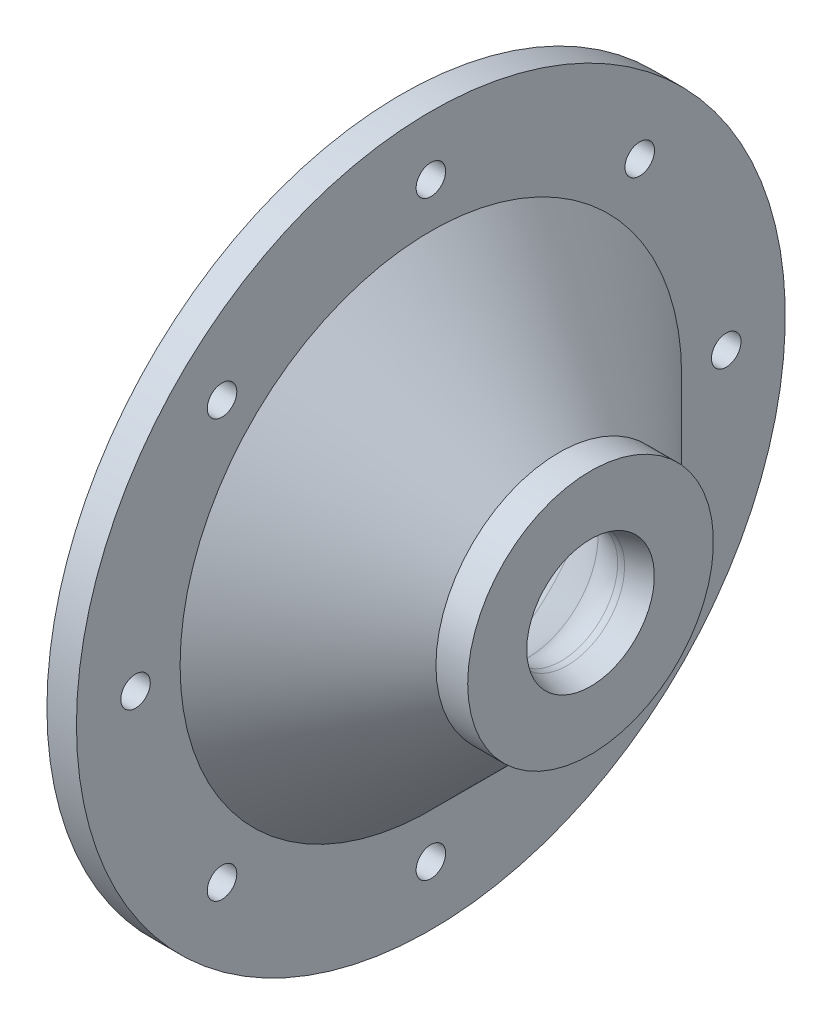
SolidWorks part; units mm, degrees
ref_plane "Front Plane" through (0, 0, 0) normal (0, 0, 1) x (1, 0, 0)
ref_plane "Top Plane" through (0, 0, 0) normal (0, 1, 0) x (1, 0, 0)
ref_plane "Right Plane" through (0, 0, 0) normal (1, 0, 0) x (0, 0, -1)
ref_axis "Axis1" through (-78.8197, 0, 0) along (1, 0, 0)
sketch "Sketch1" plane through (0, 0, 0) normal (0, 0, 1) x (1, 0, 0)
  line L1 (3.5921, 17.5621) -> (13.5703, 7.5839)
  line L2 (17.8198, 6.1825) -> (20.3406, 6.858)
  line L3 (0, 0) -> (4.5784, 0) construction
  line L4 (20.3406, 6.858) -> (20.3406, 13.208)
  line L5 (20.3406, 13.208) -> (16.9265, 13.208)
  line L6 (16.9265, 13.208) -> (3.175, 26.9595)
  line L10 (0, 19.05) -> (0, 38.1)
  line L11 (0, 38.1) -> (3.175, 38.1)
  line L12 (3.175, 38.1) -> (3.175, 26.9595)
  arc A0 (0, 19.05) -> (3.5921, 17.5621) centre (0, 13.97) cw
  arc A1 (13.5703, 7.5839) -> (17.1624, 6.096) centre (17.1624, 11.176) ccw
  arc A2 (17.1624, 6.096) -> (17.8198, 6.1825) centre (17.1624, 8.636) ccw
  point P13 (17.6181, 12.4785)
  point P16 (17.6248, 9.4173)
  point P18 (3.175, 22.4382)
  point P20 (5.8936, 19.8636)
  point P21 (7.1175, 21.0875)
  point P22 (5.6519, 19.6219)
  point P23 (3.175, 22.2985)
  point P24 (18.2958, 9.5971)
  point P25 (0, 0)
  point P26 (0, 0)
  point P27 (18.4132, 12.6915)
  point P28 (16.9593, 13.208)
  dimension "D1" = 5.08
  dimension "D6" = 2.54
  dimension "D7" = 5.08
  dimension "D4" = 6.096
  dimension "D5" = 6.858
  dimension "D9" = 19.05
  dimension "D11" = 38.1
  dimension "D12" = 3.175
  dimension "D8" = 6.35
  dimension "D10" = 6.35
  dimension "D2" = 45
  dimension "D3" = 15
revolve "Revolve1" add sketch "Sketch1" angle 360 about L3
hole_wizard "1/8 (0.125) Diameter Hole1" positions "Sketch2" profile "Sketch3" hole size "1/8" standard "ANSI Inch" end condition through all
sketch "Sketch2" plane through (3.175, 0, 0) normal (1, 0, 0) x (0, 0, -1)
  point P0 (0, 31.75)
  dimension "D1" = 31.75
sketch "Sketch3" plane through (3.175, 31.75, 0) normal (0, 1, 0) x (0, 0, -1)
  line L0 (0, 0) -> (0, 3.175)
  line L1 (0, 3.175) -> (1.5875, 3.175)
  line L2 (1.5875, 3.175) -> (1.5875, 0)
  line L5 (1.5875, 0) -> (0, 0)
  line L11 (0, -6.35) -> (0, 107.95) construction
  dimension "Thru Hole Dia." = 3.175
  dimension "Thru Hole Depth" = 3.175
pattern_circular "CirPattern1" count 8 over 360 about axis through (-78.8197, 0, 0) along (1, 0, 0) of "1/8 (0.125) Diameter Hole1"
equation "\"D4@Sketch1\"=1*.24"
equation "\"throatR\"= 0.24"
equation "\"exitR\"= .27"
equation "\"wallThickness\"= .125"
equation "\"isogridThickness\"= .125"
equation "\"D8@Sketch1\"=\"wallThickness\"+\"isogridThickness\""
equation "\"D10@Sketch1\"=\"D8@Sketch1\""
